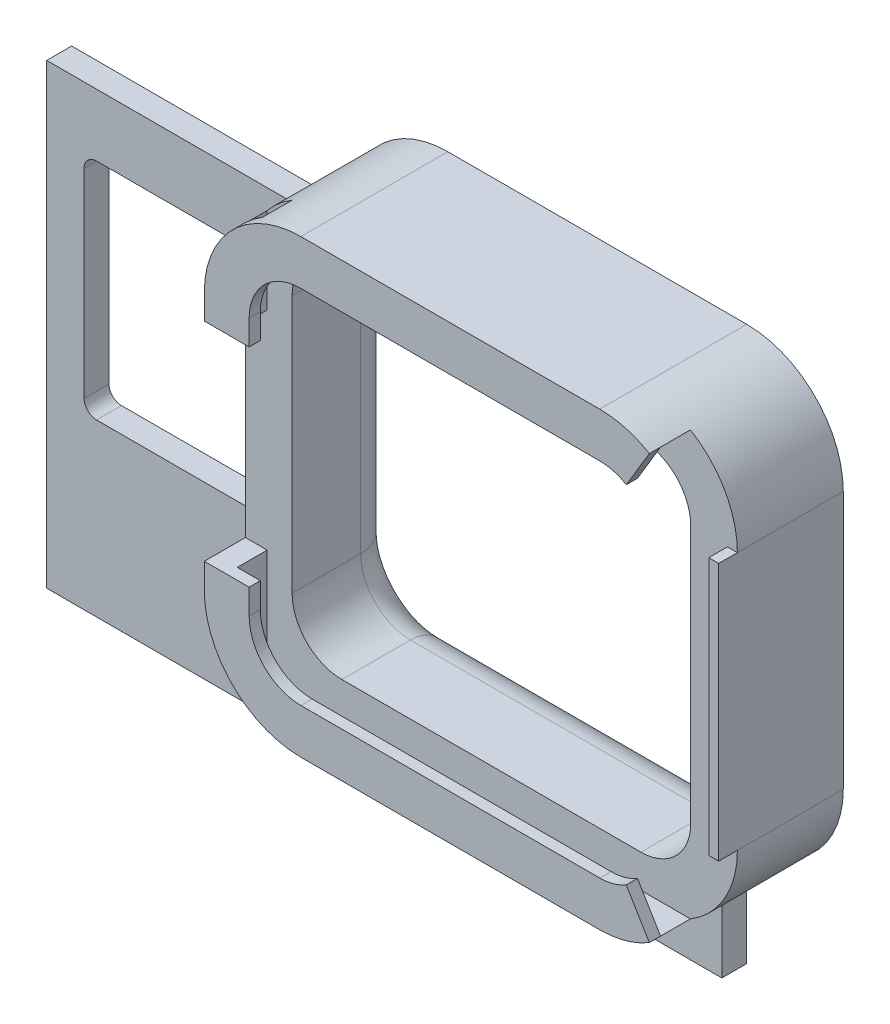
SolidWorks part; units mm, degrees
material "ABS"
ref_plane "Alzado" through (0, 0, 0) normal (0, 0, 1) x (1, 0, 0)
ref_plane "Planta" through (0, 0, 0) normal (0, 1, 0) x (1, 0, 0)
ref_plane "Vista lateral" through (0, 0, 0) normal (1, 0, 0) x (0, 0, -1)
sketch "Croquis1" plane through (0, 0, 0) normal (0, 0, 1) x (1, 0, 0)
  line L0 (-198.8372, 71.4337) -> (-144.6372, 71.4337)
  line L1 (-144.6372, 71.4337) -> (-144.6372, 79.6837)
  line L2 (-144.6372, 83.4337) -> (-168.6372, 83.4337)
  line L3 (-172.6372, 87.4337) -> (-172.6372, 108.1337)
  line L4 (-176.3872, 108.1337) -> (-198.8372, 108.1337)
  line L5 (-198.8372, 108.1337) -> (-198.8372, 71.4337)
  line L6 (-172.6372, 97.7837) -> (-156.6372, 97.7837) construction
  line L7 (-156.6372, 97.7837) -> (-156.6372, 83.4337) construction
  line L8 (-144.6372, 112.1337) -> (-168.6372, 112.1337)
  line L9 (-140.6372, 87.4337) -> (-140.6372, 108.1337)
  line L10 (-136.8872, 87.4337) -> (-136.8872, 108.1337)
  line L11 (-144.6372, 115.8837) -> (-168.6372, 115.8837)
  arc A0 (-172.6372, 87.4337) -> (-168.6372, 83.4337) centre (-168.6372, 87.4337) ccw
  arc A1 (-172.6372, 108.1337) -> (-168.6372, 112.1337) centre (-168.6372, 108.1337) cw
  arc A2 (-140.6372, 87.4337) -> (-144.6372, 83.4337) centre (-144.6372, 87.4337) cw
  arc A3 (-140.6372, 108.1337) -> (-144.6372, 112.1337) centre (-144.6372, 108.1337) ccw
  arc A4 (-136.8872, 87.4337) -> (-144.6372, 79.6837) centre (-144.6372, 87.4337) cw
  arc A5 (-136.8872, 108.1337) -> (-144.6372, 115.8837) centre (-144.6372, 108.1337) ccw
  arc A6 (-176.3872, 108.1337) -> (-168.6372, 115.8837) centre (-168.6372, 108.1337) cw
  dimension "D7" = 4
  dimension "D1" = 54.2
  dimension "D2" = 36.7
  dimension "D3" = 26.2
  dimension "D4" = 24
  dimension "D5" = 12
  dimension "D6" = 20.7
  dimension "D8" = 3.75
extrude "Saliente-Extruir1" add sketch "Croquis1" along normal blind 2
sketch "Croquis3" plane through (0, 0, 2) normal (0, 0, 1) x (1, 0, 0)
  line L28 (-136.8872, 87.4337) -> (-136.8872, 108.1337)
  line L29 (-168.6372, 79.6837) -> (-144.6372, 79.6837)
  line L30 (-176.3872, 108.1337) -> (-176.3872, 87.4337)
  line L31 (-144.6372, 115.8837) -> (-168.6372, 115.8837)
  line L50 (-140.6372, 87.4337) -> (-140.6372, 108.1337)
  line L51 (-168.6372, 83.4337) -> (-144.6372, 83.4337)
  line L52 (-144.6372, 112.1337) -> (-168.6372, 112.1337)
  line L53 (-172.6372, 108.1337) -> (-172.6372, 87.4337)
  line L54 (-140.6372, 87.4337) -> (-140.6372, 108.1337)
  line L55 (-168.6372, 83.4337) -> (-144.6372, 83.4337)
  line L56 (-144.6372, 112.1337) -> (-168.6372, 112.1337)
  line L57 (-172.6372, 108.1337) -> (-172.6372, 87.4337)
  arc A0 (-144.6372, 79.6837) -> (-136.8872, 87.4337) centre (-144.6372, 87.4337) ccw construction
  arc A1 (-136.8872, 108.1337) -> (-144.6372, 115.8837) centre (-144.6372, 108.1337) ccw construction
  arc A2 (-168.6372, 115.8837) -> (-176.3872, 108.1337) centre (-168.6372, 108.1337) ccw construction
  arc A24 (-136.8872, 108.1337) -> (-144.6372, 115.8837) centre (-144.6372, 108.1337) ccw
  arc A25 (-144.6372, 79.6837) -> (-136.8872, 87.4337) centre (-144.6372, 87.4337) ccw
  arc A26 (-176.3872, 87.4337) -> (-168.6372, 79.6837) centre (-168.6372, 87.4337) ccw
  arc A27 (-168.6372, 115.8837) -> (-176.3872, 108.1337) centre (-168.6372, 108.1337) ccw
  arc A52 (-144.6372, 83.4337) -> (-140.6372, 87.4337) centre (-144.6372, 87.4337) ccw
  arc A53 (-140.6372, 108.1337) -> (-144.6372, 112.1337) centre (-144.6372, 108.1337) ccw
  arc A54 (-168.6372, 112.1337) -> (-172.6372, 108.1337) centre (-168.6372, 108.1337) ccw
  arc A55 (-172.6372, 87.4337) -> (-168.6372, 83.4337) centre (-168.6372, 87.4337) ccw
  arc A56 (-144.6372, 83.4337) -> (-140.6372, 87.4337) centre (-144.6372, 87.4337) ccw
  arc A57 (-140.6372, 108.1337) -> (-144.6372, 112.1337) centre (-144.6372, 108.1337) ccw
  arc A58 (-168.6372, 112.1337) -> (-172.6372, 108.1337) centre (-168.6372, 108.1337) ccw
  arc A59 (-172.6372, 87.4337) -> (-168.6372, 83.4337) centre (-168.6372, 87.4337) ccw
  point P9 (-139.1572, 81.9536)
  point P11 (-139.1572, 81.9536)
  point P15 (-139.1572, 113.6137)
  point P16 (-139.1572, 113.6137)
  point P17 (-174.1173, 113.6137)
  point P22 (-174.1173, 113.6137)
  dimension "D2" = 0
extrude "Saliente-Extruir2" add sketch "Croquis3" along normal blind 6.5
ref_plane "Plano1" through (0, 89.7837, 0) normal (0, -1, 0) x (-1, 0, 0)
sketch "Croquis5" plane through (0, 108.1337, 0) normal (0, 1, 0) x (1, 0, 0)
  line L0 (-176.3872, -2) -> (-176.3872, -7)
  line L1 (-176.3872, -8.5) -> (-176.3872, -2) construction
  line L2 (-176.3872, -7) -> (-198.8372, -7)
  line L3 (-198.8372, -7) -> (-198.8372, -2)
  line L4 (-198.8372, -2) -> (-197.9872, -2)
  line L5 (-176.3872, -2) -> (-198.8372, -2) construction
  line L6 (-197.9872, -2) -> (-197.9872, -5)
  line L7 (-197.9872, -5) -> (-177.9872, -5)
  line L8 (-177.9872, -5) -> (-177.9872, -2)
  line L9 (-177.9872, -2) -> (-176.3872, -2)
  dimension "D1" = 5
  dimension "D2" = 3
  dimension "D3" = 20
  dimension "D4" = 1.6
extrude "Saliente-Extruir3" [suppressed] add sketch "Croquis5" against normal blind 5 and the other way blind 5 from surface
sketch "Croquis6" plane through (0, 0, 8.5) normal (0, 0, 1) x (1, 0, 0)
  line L0 (-141.8088, 110.9621) -> (-171.4657, 84.6052) construction
  line L1 (-172.6172, 114.7837) -> (-140.6573, 114.7837)
  line L2 (-174.6372, 80.7837) -> (-138.6372, 80.7837) construction
  line L3 (-174.6372, 80.7837) -> (-174.6372, 114.7837) construction
  line L4 (-174.6372, 114.7837) -> (-138.6372, 114.7837) construction
  line L5 (-138.6372, 80.7837) -> (-138.6372, 114.7837) construction
  line L6 (-174.6372, 80.7837) -> (-138.6372, 114.7837) construction
  line L7 (-174.6372, 114.7837) -> (-138.6372, 80.7837) construction
  line L8 (-144.6372, 115.8837) -> (-168.6372, 115.8837)
  line L9 (-156.6372, 97.7837) -> (-172.6372, 97.7837) construction
  line L10 (-172.6372, 108.1337) -> (-172.6372, 87.4337) construction
  line L11 (-156.6372, 97.7837) -> (-156.6372, 112.1337) construction
  line L12 (-144.6372, 112.1337) -> (-168.6372, 112.1337) construction
  line L13 (-144.6372, 79.6837) -> (-168.6372, 79.6837)
  line L14 (-172.6172, 80.7837) -> (-140.6573, 80.7837)
  line L15 (-174.6372, 113.039) -> (-174.6372, 106.1337)
  line L16 (-174.6372, 106.1337) -> (-176.3872, 106.1337)
  line L22 (-176.3872, 108.1337) -> (-176.3872, 87.4337) construction
  line L23 (-176.3872, 108.1337) -> (-176.3872, 106.1337)
  line L24 (-176.3872, 87.4337) -> (-176.3872, 89.4337)
  line L25 (-174.6372, 89.4337) -> (-176.3872, 89.4337)
  line L26 (-174.6372, 82.5283) -> (-174.6372, 89.4337)
  arc A0 (-140.6372, 108.1337) -> (-144.6372, 112.1337) centre (-144.6372, 108.1337) ccw construction
  arc A1 (-172.6372, 87.4337) -> (-168.6372, 83.4337) centre (-168.6372, 87.4337) ccw construction
  arc A3 (-168.6372, 115.8837) -> (-176.3872, 108.1337) centre (-168.6372, 108.1337) ccw construction
  arc A4 (-168.6372, 115.8837) -> (-172.6172, 114.7837) centre (-168.6372, 108.1337) ccw
  arc A5 (-144.6372, 115.8837) -> (-140.6573, 114.7837) centre (-144.6372, 108.1337) cw
  arc A6 (-168.6372, 79.6837) -> (-172.6172, 80.7837) centre (-168.6372, 87.4337) cw
  arc A7 (-144.6372, 79.6837) -> (-140.6573, 80.7837) centre (-144.6372, 87.4337) ccw
  arc A8 (-176.3872, 108.1337) -> (-174.6372, 113.039) centre (-168.6372, 108.1337) cw
  arc A11 (-136.8872, 108.1337) -> (-144.6372, 115.8837) centre (-144.6372, 108.1337) ccw construction
  arc A12 (-176.3872, 87.4337) -> (-174.6372, 82.5283) centre (-168.6372, 87.4337) ccw
  point P8 (-156.6372, 97.7837)
  dimension "D1" = 36
  dimension "D2" = 34
  dimension "D3" = 2
extrude "Saliente-Extruir4" add sketch "Croquis6" along normal blind 2.4
sketch "Croquis7" plane through (0, 0, 8.5) normal (0, 0, 1) x (1, 0, 0)
  line L2 (-172.7872, 106.1337) -> (-172.7872, 108.1337)
  line L3 (-168.6372, 112.2837) -> (-144.6372, 112.2837)
  line L5 (-172.7872, 106.1337) -> (-176.3872, 106.1337)
  line L6 (-140.8878, 97.7837) -> (-172.6372, 97.7837) construction
  line L7 (-172.6372, 108.1337) -> (-172.6372, 87.4337) construction
  line L8 (-168.6372, 79.6837) -> (-144.6372, 79.6837)
  line L9 (-176.3872, 106.1337) -> (-176.3872, 108.1337)
  line L10 (-168.6372, 115.8837) -> (-144.6372, 115.8837)
  line L11 (-176.3872, 89.4337) -> (-176.3872, 87.4337)
  line L12 (-172.7872, 89.4337) -> (-176.3872, 89.4337)
  line L14 (-168.6372, 83.2837) -> (-144.6372, 83.2837)
  line L15 (-172.7872, 89.4337) -> (-172.7872, 87.4337)
  line L17 (-140.6573, 114.7837) -> (-142.506, 111.6946)
  line L18 (-140.6573, 80.7837) -> (-142.506, 83.8727)
  line L19 (-140.4873, 108.1484) -> (-140.8878, 97.7837) construction
  line L20 (-136.8875, 108.0735) -> (-137.2905, 97.6446) construction
  arc A0 (-172.7872, 108.1337) -> (-168.6372, 112.2837) centre (-168.6372, 108.1337) cw
  arc A1 (-144.6372, 112.2837) -> (-142.506, 111.6946) centre (-144.6372, 108.1337) cw
  arc A2 (-144.6372, 79.6837) -> (-140.6573, 80.7837) centre (-144.6372, 87.4337) ccw
  arc A3 (-176.3872, 87.4337) -> (-168.6372, 79.6837) centre (-168.6372, 87.4337) ccw
  arc A4 (-176.3872, 108.1337) -> (-168.6372, 115.8837) centre (-168.6372, 108.1337) cw
  arc A5 (-144.6372, 115.8837) -> (-140.6573, 114.7837) centre (-144.6372, 108.1337) cw
  arc A6 (-144.6372, 83.2837) -> (-142.506, 83.8727) centre (-144.6372, 87.4337) ccw
  arc A7 (-172.7872, 87.4337) -> (-168.6372, 83.2837) centre (-168.6372, 87.4337) ccw
  arc A9 (-144.6372, 112.2837) -> (-140.4873, 108.1484) centre (-144.6372, 108.1337) cw construction
  arc A10 (-144.6372, 115.8837) -> (-136.8875, 108.0735) centre (-144.6372, 108.1337) cw construction
  dimension "D1" = 3.6
extrude "Saliente-Extruir5" add sketch "Croquis7" along normal blind 0.9 from surface starting at face at (-156.6372, 115.4686, 10.9)
fillet "Redondeo1" radius 3 8 edges at (-171.4657, 110.9621, 0) (-156.6372, 112.1337, 0) (-141.8088, 110.9621, 0) (-140.6372, 97.7837, 0) (-141.8088, 84.6052, 0) (-156.6372, 83.4337, 0) (-171.4657, 84.6052, 0) (-172.6372, 97.7837, 0)
sketch "Croquis8" plane through (0, 0, 8.5) normal (0, 0, 1) x (1, 0, 0)
  line L0 (-136.8872, 108.1337) -> (-136.8872, 87.4337)
  line L1 (-136.8872, 87.4337) -> (-137.6872, 87.4337)
  line L2 (-137.6872, 87.4337) -> (-137.6872, 108.1337)
  line L3 (-137.6872, 108.1337) -> (-136.8872, 108.1337)
  dimension "D1" = 0.8
extrude "Saliente-Extruir6" add sketch "Croquis8" along normal blind 1.5
sketch "Croquis9" plane through (0, 0, 2) normal (0, 0, 1) x (1, 0, 0)
  line L0 (-176.3872, 108.1337) -> (-198.8372, 108.1337) construction
  line L1 (-195.8372, 103.1337) -> (-177.8372, 103.1337)
  line L2 (-195.8372, 103.1337) -> (-195.8372, 85.1337)
  line L3 (-195.8372, 85.1337) -> (-177.8372, 85.1337)
  line L4 (-177.8372, 103.1337) -> (-177.8372, 85.1337)
  line L5 (-198.8372, 108.1337) -> (-198.8372, 71.4337) construction
  dimension "D1" = 18
  dimension "D2" = 5
  dimension "D3" = 3
  dimension "D4" = 18
extrude "Cortar-Extruir1" cut sketch "Croquis9" against normal up to surface (2 mm away) up to face at (-156.6372, 97.7837, 0)
fillet "Redondeo2" radius 1 4 edges at (-177.8372, 103.1337, 1) (-177.8372, 85.1337, 1) (-195.8372, 85.1337, 1) (-195.8372, 103.1337, 1)
